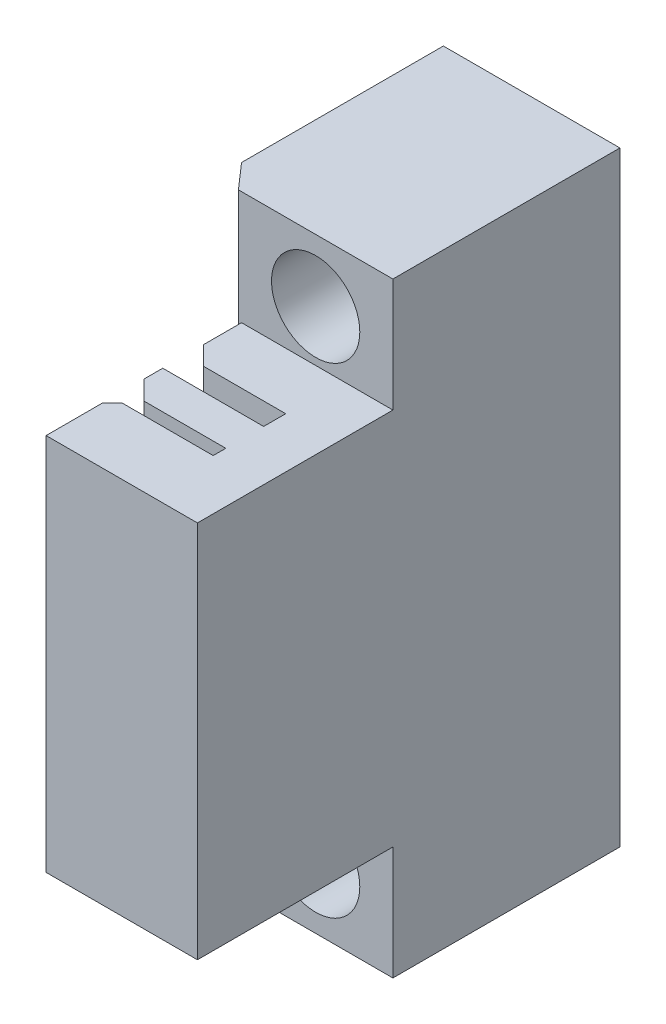
SolidWorks part; units mm, degrees
ref_plane "Front Plane" through (0, 0, 0) normal (0, 0, 1) x (1, 0, 0)
ref_plane "Top Plane" through (0, 0, 0) normal (0, 1, 0) x (1, 0, 0)
ref_plane "Right Plane" through (0, 0, 0) normal (1, 0, 0) x (0, 0, -1)
sketch "Sketch1" plane through (0, 0, 0) normal (0, 1, 0) x (1, 0, 0)
  line L9 (0, 0) -> (14, 0)
  line L10 (14, 0) -> (14, -18)
  line L11 (14, -18) -> (1.75, -18)
  line L12 (1.75, -18) -> (0, -16)
  line L13 (0, -16) -> (0, 0)
  dimension "D1" = 14
  dimension "D2" = 18
  dimension "D3" = 16
  dimension "D4" = 12.25
extrude "Boss-Extrude1" add sketch "Sketch1" along normal mid plane 48
sketch "Sketch2" plane through (0, 0, 0) normal (0, 1, 0) x (1, 0, 0)
  line L0 (14, -18) -> (14, -33.5)
  line L1 (14, -33.5) -> (2, -33.5)
  line L2 (2, -33.5) -> (2, -29.25)
  line L3 (2, -29.25) -> (10, -29.25)
  line L4 (10, -29.25) -> (10, -27.25)
  line L5 (10, -27.25) -> (3.5, -27.25)
  line L6 (3.5, -27.25) -> (2, -25.75)
  line L7 (2, -25.75) -> (2, -24.25)
  line L8 (2, -24.25) -> (10, -24.25)
  line L9 (10, -24.25) -> (10, -22.5)
  line L10 (10, -22.5) -> (3.5, -22.5)
  line L11 (3.5, -22.5) -> (2, -21)
  line L12 (2, -21) -> (2, -18)
  line L13 (2, -18) -> (14, -18)
  dimension "D1" = 15.5
  dimension "D2" = 12
  dimension "D3" = 4.25
  dimension "D4" = 3
  dimension "D5" = 4.5
  dimension "D6" = 2
  dimension "D7" = 135
  dimension "D8" = 1.5
  dimension "D9" = 1.5
  dimension "D10" = 8
extrude "Boss-Extrude2" add sketch "Sketch2" along normal mid plane 30
sketch "Sketch3" plane through (10, 0, 0) normal (-1, 0, 0) x (0, 0, 1)
  line L1 (29.25, 15) -> (28.25, 15)
  line L2 (29.25, 15) -> (29.25, 14)
  line L3 (29.25, 14) -> (28.25, 14)
  line L4 (28.25, 15) -> (28.25, 14)
  dimension "D1" = 1
  dimension "D2" = 1
extrude "Boss-Extrude3" add sketch "Sketch3" along normal up to surface (8 mm away) up to face at (2, 0, 31.375)
chamfer "Chamfer1" distance 0.75 angle 45 1 edges at (2, 14.5, 28.25)
pattern_linear "LPattern1" count 15 spacing 2 along (0, -1, 0) of "Chamfer1", "Boss-Extrude3"
sketch "Sketch5" plane through (10, 0, 0) normal (-1, 0, 0) x (0, 0, 1)
  line L1 (24.25, -15) -> (23.25, -15)
  line L2 (24.25, -15) -> (24.25, -14)
  line L3 (24.25, -14) -> (23.25, -14)
  line L4 (23.25, -15) -> (23.25, -14)
  dimension "D1" = 1
  dimension "D2" = 1
extrude "Boss-Extrude4" add sketch "Sketch5" along normal up to surface (8 mm away) up to face at (2, 0, 25)
chamfer "Chamfer2" distance 0.75 angle 45 1 edges at (2, -14.5, 23.25)
pattern_linear "LPattern2" count 15 spacing 2 along (0, 1, 0) of "Chamfer2", "Boss-Extrude4"
sketch "Sketch6" plane through (0, 0, 18) normal (0, 0, 1) x (1, 0, 0)
  line L0 (7.875, 24) -> (7.875, -24) construction
  line L1 (1.75, 24) -> (14, 24) construction
  line L2 (1.75, -24) -> (14, -24) construction
  line L3 (7.875, 0) -> (16.575, 0) construction
  circle A0 centre (7.875, 19.05) radius 1.6117
  circle A1 centre (7.875, -19.05) radius 1.578
  dimension "D1" = 38.1
  dimension "D2" = 19.05
extrude "Cut-Extrude1" cut sketch "Sketch6" against normal blind 30
sketch "Sketch7" plane through (0, 0, 18) normal (0, 0, 1) x (1, 0, 0)
  circle A0 centre (7.875, 19.05) radius 3.5
  circle A1 centre (7.875, -19.05) radius 3.5
  dimension "D1" = 7
  dimension "D2" = 7
extrude "Cut-Extrude2" cut sketch "Sketch7" against normal blind 7
